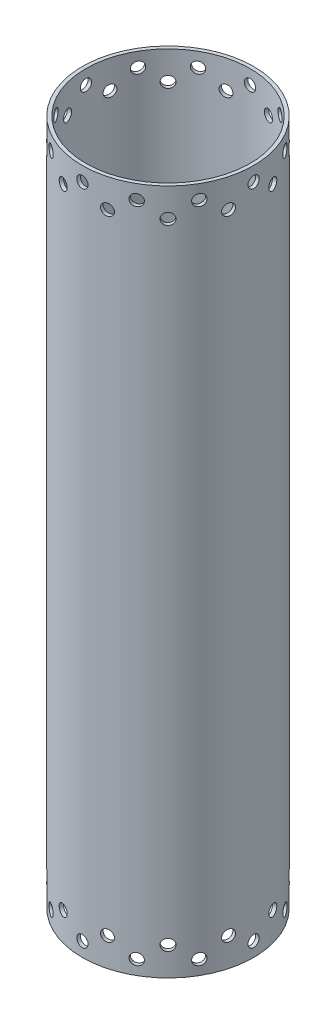
SolidWorks part; units mm, degrees
material "6061-T6 (SS)"
ref_plane "Front Plane" through (0, 0, 0) normal (0, 0, 1) x (1, 0, 0)
ref_plane "Top Plane" through (0, 0, 0) normal (0, 1, 0) x (1, 0, 0)
ref_plane "Right Plane" through (0, 0, 0) normal (1, 0, 0) x (0, 0, -1)
sketch "Sketch2" plane through (0, 0, 0) normal (0, 1, 0) x (1, 0, 0)
  circle A0 centre (0, 0) radius 76.2
  circle A1 centre (0, 0) radius 73.025
  dimension "D1" = 152.4
  dimension "D2" = 3.175
extrude "Boss-Extrude1" add sketch "Sketch2" along normal blind 609.6
sketch "Sketch3" plane through (0, 0, 0) normal (0, 0, 1) x (1, 0, 0)
  line L0 (0, 609.6) -> (0, 596.9) construction
  line L1 (73.025, 609.6) -> (-73.025, 609.6) construction
  circle A0 centre (0, 596.9) radius 5.0419
  dimension "D1" = 10.0838
  dimension "D2" = 12.7
extrude "Cut-Extrude1" cut sketch "Sketch3" against normal blind 1143
ref_plane "Plane1" through (-19.722, 0, 73.6035) normal (-0.2588, 0, 0.9659) x (0, -1, 0)
sketch "Sketch6" plane through (-19.722, 0, 73.6035) normal (-0.2588, 0, 0.9659) x (0, -1, 0)
  line L0 (-609.6, 0) -> (-584.2, 0) construction
  line L1 (-609.6, 76.2) -> (-609.6, -76.2) construction
  circle A0 centre (-584.2, 0) radius 5.0419
  dimension "D1" = 10.0838
extrude "Cut-Extrude2" cut sketch "Sketch6" against normal blind 25.4
pattern_circular "CirPattern2" count 12 over 360 about axis through (0, 609.6, 0) along (0, -1, 0) of "Cut-Extrude2", "Cut-Extrude1"
ref_plane "Plane2" through (0, 304.8, 0) normal (0, 1, 0) x (1, 0, 0)
mirror "Mirror1" about plane through (0, 304.8, 0) normal (0, 1, 0) of "CirPattern2"
equation "\"holeDia\"=0.397"
equation "\"D1@Sketch3\"=\"holeDia\""
equation "\"D1@Sketch6\"=\"holeDia\""
equation "\"numHoles\"=12"
equation "\"D1@CirPattern2\"=\"numHoles\""
equation "\"D1@Plane1\"=180/\"numHoles\""
